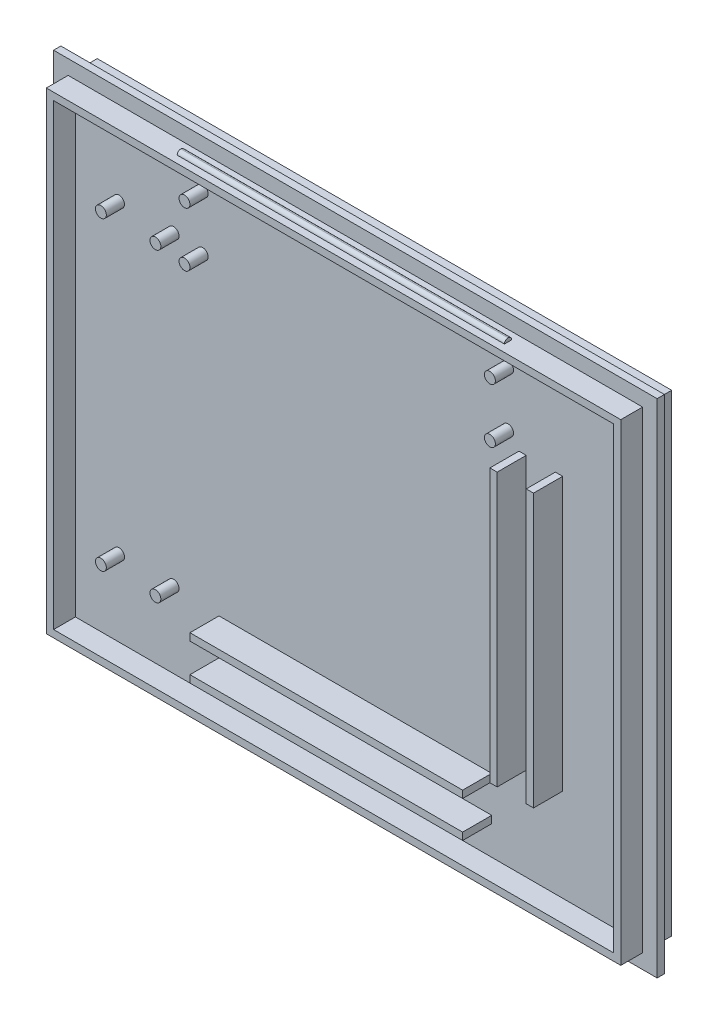
SolidWorks part; units mm, degrees
ref_plane "정면" through (0, 0, 0) normal (0, 0, 1) x (1, 0, 0)
ref_plane "윗면" through (0, 0, 0) normal (0, 1, 0) x (1, 0, 0)
ref_plane "우측면" through (0, 0, 0) normal (1, 0, 0) x (0, 0, -1)
sketch "스케치1" plane through (0, 0, 0) normal (0, 0, 1) x (1, 0, 0)
  line L1 (-83, -69) -> (83, -69)
  line L2 (-83, -69) -> (-83, 69)
  line L3 (-83, 69) -> (83, 69)
  line L4 (83, -69) -> (83, 69)
  line L5 (-83, -69) -> (83, 69) construction
  line L6 (-83, 69) -> (83, -69) construction
  point P0 (0, 0)
  dimension "D1" = 138
  dimension "D2" = 166
extrude "보스-돌출1" add sketch "스케치1" along normal blind 2
sketch "스케치2" plane through (0, 0, 2) normal (0, 0, 1) x (1, 0, 0)
  line L1 (78, -64) -> (-78, -64)
  line L2 (78, -64) -> (78, 64)
  line L3 (78, 64) -> (-78, 64)
  line L4 (-78, -64) -> (-78, 64)
  line L5 (78, -64) -> (-78, 64) construction
  line L6 (78, 64) -> (-78, -64) construction
  point P0 (0, 0)
  dimension "D1" = 156
  dimension "D2" = 128
extrude "돌출-얇게2" add sketch "스케치2" along normal blind 6 and the other way blind 8 thin thin type mid plane wall 2
sketch "스케치3" plane through (0, 0, 2) normal (0, 0, 1) x (1, 0, 0)
  line L0 (-77, 63) -> (-77, -63) construction
  line L1 (-77, -63) -> (77, -63) construction
  line L2 (0, 0) -> (-60.4679, 0) construction
  circle A0 centre (-65, -42) radius 1.5
  circle A1 centre (-50, -42) radius 1.5
  circle A2 centre (-65, 42) radius 1.5
  circle A3 centre (-50, 42) radius 1.5
  dimension "D1" = 12
  dimension "D2" = 21
  dimension "D3" = 15
extrude "보스-돌출2" add sketch "스케치3" along normal blind 5
sketch "스케치4" plane through (0, 0, 2) normal (0, 0, 1) x (1, 0, 0)
  line L0 (-77, 63) -> (-77, -63) construction
  line L1 (77, 63) -> (-77, 63) construction
  circle A0 centre (-42, 56) radius 1.5
  circle A1 centre (-42, 41) radius 1.5
  dimension "D1" = 35
  dimension "D2" = 7
  dimension "15" = 15
sketch "스케치5" plane through (0, 0, 2) normal (0, 0, 1) x (1, 0, 0)
  line L0 (0, 0) -> (0, 44.9945) construction
  line L1 (77, -63) -> (77, 63) construction
  line L2 (77, 63) -> (-77, 63) construction
  circle A0 centre (42, 56) radius 1.5
  circle A1 centre (42, 41) radius 1.5
  dimension "D1" = 3
  dimension "D3" = 7
  dimension "D4" = 35
  dimension "D5" = 3
  dimension "D6" = 15
  dimension "D2" = 35
extrude "보스-돌출3" add sketch "스케치5" along normal blind 5 contours A1 | A0
extrude "보스-돌출4" add sketch "스케치4" along normal blind 5 contours A1 | A0
sketch "스케치6" plane through (0, 0, 2) normal (0, 0, 1) x (1, 0, 0)
  line L0 (-77, -63) -> (77, -63) construction
  line L1 (-37.5, -53) -> (37.5, -53)
  line L2 (-37.5, -53) -> (-37.5, -55)
  line L3 (-37.5, -55) -> (37.5, -55)
  line L4 (37.5, -53) -> (37.5, -55)
  line L5 (-37.5, -53) -> (37.5, -55) construction
  line L6 (-37.5, -55) -> (37.5, -53) construction
  line L7 (77, -63) -> (77, 63) construction
  line L8 (37.5, -43) -> (-37.5, -43)
  line L9 (37.5, -43) -> (37.5, -45)
  line L10 (37.5, -45) -> (-37.5, -45)
  line L11 (-37.5, -43) -> (-37.5, -45)
  line L12 (37.5, -43) -> (-37.5, -45) construction
  line L13 (37.5, -45) -> (-37.5, -43) construction
  line L18 (47, -37.5) -> (45, -37.5)
  line L19 (47, -37.5) -> (47, 37.5)
  line L20 (47, 37.5) -> (45, 37.5)
  line L21 (45, -37.5) -> (45, 37.5)
  line L22 (47, -37.5) -> (45, 37.5) construction
  line L23 (47, 37.5) -> (45, -37.5) construction
  line L26 (57, -37.5) -> (55, -37.5)
  line L27 (57, -37.5) -> (57, 37.5)
  line L28 (57, 37.5) -> (55, 37.5)
  line L29 (55, -37.5) -> (55, 37.5)
  line L30 (57, -37.5) -> (55, 37.5) construction
  line L31 (57, 37.5) -> (55, -37.5) construction
  point P0 (0, -54)
  point P8 (0, -44)
  point P14 (46, 0)
  point P21 (77, 0)
  point P24 (56, 0)
  dimension "D1" = 8
  dimension "D2" = 2
  dimension "D3" = 75
  dimension "D4" = 0
  dimension "D5" = 8
  dimension "D6" = 2
  dimension "D7" = 30
  dimension "D8" = 2
  dimension "D9" = 75
  dimension "D10" = 0
  dimension "D11" = 8
  dimension "D12" = 2
extrude "보스-돌출5" add sketch "스케치6" along normal blind 8
sketch "스케치9" plane through (0, -65, 0) normal (0, -1, 0) x (1, 0, 0)
  line L0 (79, 2) -> (-79, 2) construction
  line L1 (-45, 6) -> (45, 6)
  line L2 (-45, 6) -> (-45, 4)
  line L3 (-45, 4) -> (45, 4)
  line L4 (45, 6) -> (45, 4)
  line L5 (-45, 6) -> (45, 4) construction
  line L6 (-45, 4) -> (45, 6) construction
  point P0 (0, 5)
  dimension "D1" = 90
  dimension "D2" = 0
  dimension "D3" = 2
  dimension "D4" = 3
extrude "보스-돌출6" add sketch "스케치9" along normal blind 1
sketch "스케치11" plane through (0, 65, 0) normal (0, 1, 0) x (1, 0, 0)
  line L0 (-79, -2) -> (79, -2) construction
  line L1 (-45, -6) -> (45, -6)
  line L2 (-45, -6) -> (-45, -4)
  line L3 (-45, -4) -> (45, -4)
  line L4 (45, -6) -> (45, -4)
  line L5 (-45, -6) -> (45, -4) construction
  line L6 (-45, -4) -> (45, -6) construction
  point P0 (0, -5)
  dimension "D1" = 90
  dimension "D2" = 0
  dimension "D3" = 2
  dimension "D4" = 3
fillet "필렛1" radius 1 2 edges at (0, -66, 4) (0, -66, 6)
extrude "보스-돌출7" add sketch "스케치11" along normal blind 1
fillet "필렛2" radius 1 2 edges at (0, 66, 4) (0, 66, 6)
